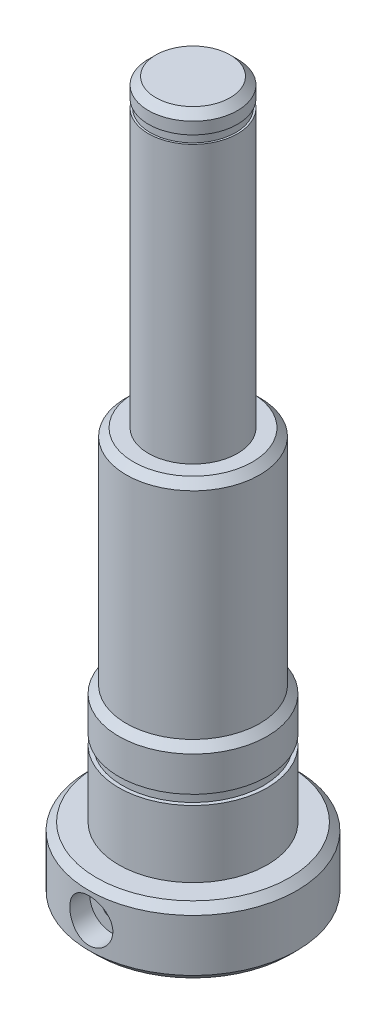
SolidWorks part; units mm, degrees
ref_plane "Front Plane" through (0, 0, 0) normal (0, 0, 1) x (1, 0, 0)
ref_plane "Top Plane" through (0, 0, 0) normal (0, 1, 0) x (1, 0, 0)
ref_plane "Right Plane" through (0, 0, 0) normal (1, 0, 0) x (0, 0, -1)
ref_axis "X" through (88.99, 0, 0) along (-1, 0, 0)
ref_axis "Y" through (0, 55, 0) along (0, -1, 0)
ref_axis "Z" through (0, 0, -88.99) along (0, 0, 1)
sketch "Sketch1" plane through (0, 0, 0) normal (0, 0, 1) x (1, 0, 0)
  line L0 (0, 0) -> (-61.4788, 0) construction
  line L1 (0, 0) -> (0, 96) construction
  line L2 (0, 0) -> (-10, 0)
  line L3 (-10, 9) -> (-10, 18)
  line L4 (-10, 25) -> (-9, 25)
  line L5 (-6, 55) -> (-6, 92.3)
  line L6 (-6, 96) -> (0, 96)
  line L7 (0, 96) -> (0, 0)
  line L10 (-9, 25) -> (-9, 55)
  line L11 (-9, 55) -> (-6, 55)
  line L12 (-10, 19.3) -> (-10, 25)
  line L13 (-10, 0) -> (-14, 0)
  line L15 (-10, 9) -> (-14, 9)
  line L16 (-14, 0) -> (-14, 9)
  line L17 (-10, 19.3) -> (-9.5, 19.3)
  line L19 (-10, 18) -> (-9.5, 18)
  line L20 (-9.5, 19.3) -> (-9.5, 18)
  line L21 (-6, 93.4) -> (-6, 96)
  line L22 (-6, 92.3) -> (-5.75, 92.3)
  line L24 (-6, 93.4) -> (-5.75, 93.4)
  line L25 (-5.75, 92.3) -> (-5.75, 93.4)
  point P24 (-5.875, 93.4)
  dimension "D1" = 12
  dimension "D2" = 20
  dimension "D3" = 9
  dimension "D4" = 9
  dimension "D5" = 25
  dimension "D6" = 96
  dimension "D7" = 55
  dimension "D8" = 18
  dimension "D10" = 4
  dimension "D12" = 9.5
  dimension "D13" = 1.3
  dimension "D14" = 37.3
  dimension "D15" = 5.75
  dimension "D16" = 1.1
revolve "Revolve1" add sketch "Sketch1" angle 360 about L1
chamfer "Chamfer2" distance 1 angle 45 1 edges at (6, 96, 0)
chamfer "Chamfer7" distance 1 angle 45 1 edges at (9, 55, 0)
chamfer "Chamfer8" distance 1 angle 45 1 edges at (10, 25, 0)
chamfer "Chamfer9" distance 1 angle 45 2 edges at (14, 0, 0) (14, 9, 0)
sketch "Sketch2" plane through (0, 0, 0) normal (0, -1, 0) x (1, 0, 0)
  line L1 (-3.0826, 4) -> (3.0826, 4) construction
  circle A0 centre (0, 0) radius 5.05
  dimension "D1" = 10.1
  dimension "D2" = 4
extrude "Cut-Extrude1" cut sketch "Sketch2" against normal blind 20.5
ref_plane "Plane1" through (0, 0, 14) normal (0, 0, 1) x (1, 0, 0)
sketch "Sketch3" plane through (0, 0, 14) normal (0, 0, 1) x (1, 0, 0)
  line L0 (0, 55) -> (0, -55) construction
  line L1 (-14, 1) -> (14, 1) construction
  circle A0 centre (0, 4.5) radius 2.9
  point P2 (0, 0)
  point P5 (0, 5.1138)
  dimension "D1" = 5.8
  dimension "D2" = 3.5
extrude "Cut-Extrude2" cut sketch "Sketch3" against normal blind 3 contours A0
sketch "Sketch4" plane through (0, 0, 11) normal (0, 0, 1) x (1, 0, 0)
  point P0 (0, 4.5)
  point P1 (0, 0)
hole_wizard "Tap Drill for M3 Tap1" positions "3DSketch1" profile "Sketch5" hole size "M3" standard "DIN"
sketch3d "3DSketch1"
  point P0 (0, 4.5, 11)
sketch "Sketch5" plane through (0, 4.5, 11) normal (1, 0, 0) x (0, -1, 0)
  line L0 (0, 0) -> (0, 8.7511)
  line L1 (0, 8.7511) -> (1.25, 8)
  line L2 (1.25, 8) -> (1.25, 0)
  line L5 (1.25, 0) -> (0, 0)
  line L10 (0, 8.7511) -> (-1.25, 8) construction
  line L11 (0, -6.35) -> (0, 107.95) construction
  dimension "Hole Dia." = 2.5
  dimension "Hole Depth" = 8
  dimension "Drill Angle" = 118
